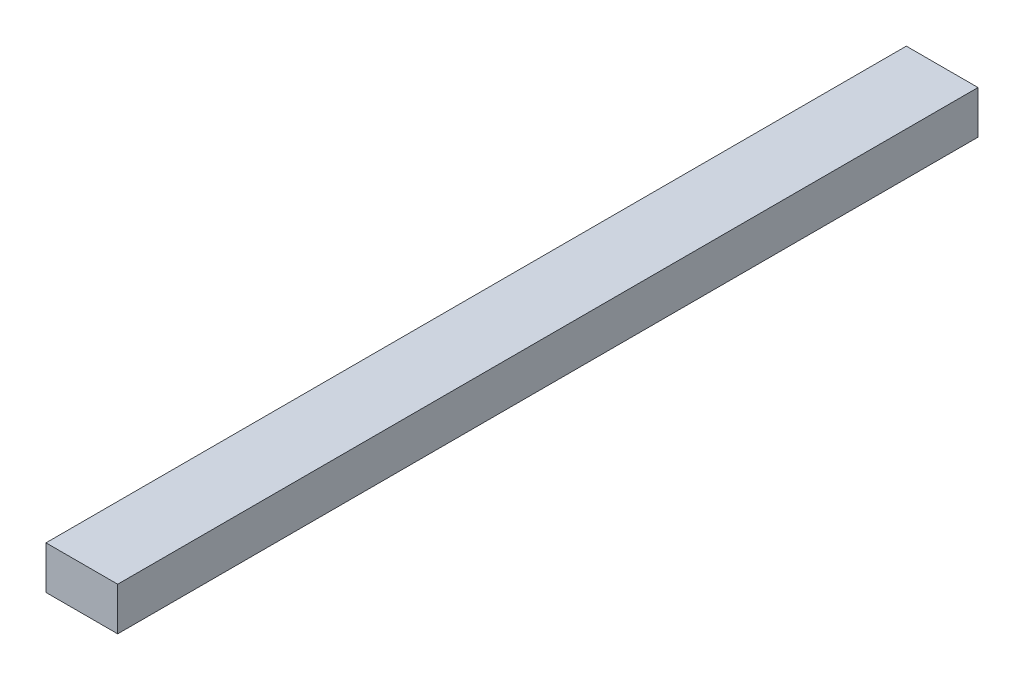
SolidWorks part; units mm, degrees
material "Красное дерево"
ref_plane "Спереди" through (0, 0, 0) normal (0, 0, 1) x (1, 0, 0)
ref_plane "Сверху" through (0, 0, 0) normal (0, 1, 0) x (1, 0, 0)
ref_plane "Справа" through (0, 0, 0) normal (1, 0, 0) x (0, 0, -1)
sketch "Эскиз1" plane through (0, 0, 0) normal (0, 0, 1) x (1, 0, 0)
  line L1 (-25, -15) -> (25, -15)
  line L2 (-25, -15) -> (-25, 15)
  line L3 (-25, 15) -> (25, 15)
  line L4 (25, -15) -> (25, 15)
  line L5 (0, 15) -> (0, -15) construction
  line L6 (-25, 0) -> (25, 0) construction
  point P0 (0, 0)
  dimension "D1" = 50
  dimension "D2" = 30
extrude "Бобышка-Вытянуть1" add sketch "Эскиз1" along normal mid plane 600
